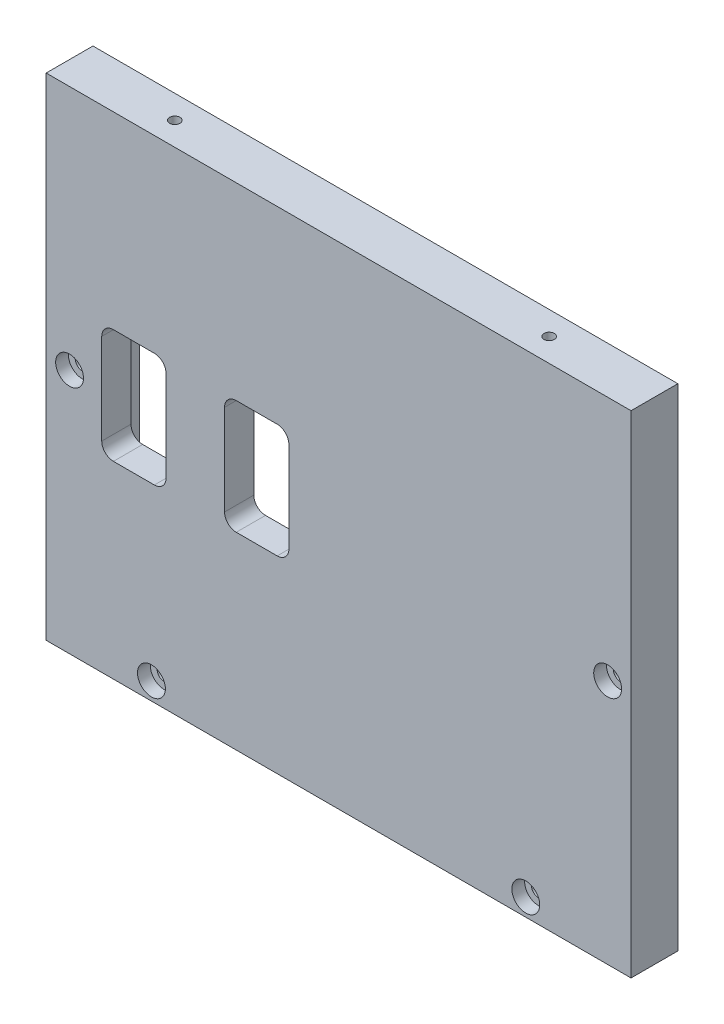
SolidWorks part; units mm, degrees
ref_plane "Front Plane" through (0, 0, 0) normal (0, 0, 1) x (1, 0, 0)
ref_plane "Top Plane" through (0, 0, 0) normal (0, 1, 0) x (1, 0, 0)
ref_plane "Right Plane" through (0, 0, 0) normal (1, 0, 0) x (0, 0, -1)
sketch "Sketch1" plane through (0, 0, 0) normal (0, 0, 1) x (1, 0, 0)
  line L1 (-50, 42) -> (50, 42)
  line L2 (-50, 42) -> (-50, -42)
  line L3 (-50, -42) -> (50, -42)
  line L4 (50, 42) -> (50, -42)
  line L5 (-50, 42) -> (50, -42) construction
  line L6 (-50, -42) -> (50, 42) construction
  point P0 (0, 0)
extrude "Boss-Extrude1" add sketch "Sketch1" along normal blind 8
sketch "Sketch2" plane through (0, 0, 8) normal (0, 0, 1) x (1, 0, 0)
  line L0 (-50, -42) -> (-50, -36) construction
  line L1 (-50, -36) -> (50, -36) construction
  line L2 (50, -42) -> (50, 42) construction
  line L3 (50, -36) -> (50, -42) construction
  line L4 (-50, -39) -> (-32, -39) construction
  line L5 (50, -39) -> (32, -39) construction
  point P12 (0, 0)
  point P13 (0, 0)
hole_wizard "CBORE for #2 Socket Head Cap Screw1" positions "3DSketch1" profile "Sketch3" counterbore size "#2" standard "ANSI Inch"
sketch3d "3DSketch1"
  point P0 (-32, -39, 8)
  point P3 (32, -39, 8)
sketch "Sketch3" plane through (-32, -39, 8) normal (1, 0, 0) x (0, -1, 0)
  line L0 (0, 0) -> (0, 13.0026)
  line L1 (0, 13.0026) -> (1.2192, 12.27)
  line L2 (1.2192, 12.27) -> (1.2192, 2.1844)
  line L3 (1.2192, 2.1844) -> (2.3812, 2.1844)
  line L4 (2.3812, 2.1844) -> (2.3812, 0)
  line L5 (2.3812, 0) -> (0, 0)
  line L10 (0, 13.0026) -> (-1.2192, 12.27) construction
  line L11 (0, -6.35) -> (0, 107.95) construction
  dimension "Hole Dia." = 2.4384
  dimension "Hole Depth" = 12.27
  dimension "C'Bore Dia." = 4.7625
  dimension "C'Bore Depth" = 2.1844
  dimension "Drill Angle" = 118
sketch "Sketch4" plane through (0, 0, 8) normal (0, 0, 1) x (1, 0, 0)
  line L0 (-50, -42) -> (-42, -42) construction
  line L1 (-42, -42) -> (-42, 42) construction
  line L2 (50, 42) -> (-50, 42) construction
  line L3 (-42, 42) -> (-50, 42) construction
  line L4 (50, -42) -> (42, -42) construction
  line L5 (42, -42) -> (42, 42) construction
  line L6 (42, 42) -> (50, 42) construction
  line L7 (46, -42) -> (46, 0) construction
  line L8 (-46, -42) -> (-46, 0) construction
hole_wizard "CBORE for #2 Socket Head Cap Screw2" positions "3DSketch2" profile "Sketch5" counterbore size "#2" standard "ANSI Inch"
sketch3d "3DSketch2"
  point P0 (-46, 0, 8)
  point P3 (46, 0, 8)
sketch "Sketch5" plane through (-46, 0, 8) normal (1, 0, 0) x (0, -1, 0)
  line L0 (0, 0) -> (0, 13.0026)
  line L1 (0, 13.0026) -> (1.2192, 12.27)
  line L2 (1.2192, 12.27) -> (1.2192, 2.1844)
  line L3 (1.2192, 2.1844) -> (2.3812, 2.1844)
  line L4 (2.3812, 2.1844) -> (2.3812, 0)
  line L5 (2.3812, 0) -> (0, 0)
  line L10 (0, 13.0026) -> (-1.2192, 12.27) construction
  line L11 (0, -6.35) -> (0, 107.95) construction
  dimension "Hole Dia." = 2.4384
  dimension "Hole Depth" = 12.27
  dimension "C'Bore Dia." = 4.7625
  dimension "C'Bore Depth" = 2.1844
  dimension "Drill Angle" = 118
sketch "Sketch6" plane through (0, 42, 0) normal (0, 1, 0) x (1, 0, 0)
  line L0 (-50, -4) -> (-32, -4) construction
  line L1 (-50, -8) -> (-50, 0) construction
  line L2 (50, -4) -> (32, -4) construction
  line L3 (50, -8) -> (50, 0) construction
hole_wizard "#2-56 Tapped Hole1" positions "3DSketch3" profile "Sketch7" tap size "#2-56" standard "ANSI Inch"
sketch3d "3DSketch3"
  point P0 (-32, 42, 4)
  point P3 (32, 42, 4)
sketch "Sketch7" plane through (-32, 42, 4) normal (1, 0, 0) x (0, 0, 1)
  line L0 (0, 0) -> (0, 12.5342)
  line L1 (0, 12.5342) -> (0.889, 12)
  line L2 (0.889, 12) -> (0.889, 0)
  line L5 (0.889, 0) -> (0, 0)
  line L10 (0, 12.5342) -> (-0.889, 12) construction
  line L11 (0, -6.35) -> (0, 107.95) construction
  dimension "Tap Drill Dia." = 1.778
  dimension "Tap Drill Depth" = 12
  dimension "Drill Angle" = 118
cosmetic thread "Hole Thread1" parameters "D1"=10, "D2"=2.1844
cosmetic thread "Hole Thread2" parameters "D1"=10, "D2"=2.1844
sketch "Sketch8" plane through (0, 0, 0) normal (0, 0, -1) x (-1, 0, 0)
  line L0 (-50, -42) -> (-50, -30) construction
  line L1 (-50, -30) -> (50, -30) construction
  line L2 (50, 42) -> (50, -42) construction
  line L3 (50, -30) -> (50, -42) construction
sketch "Sketch9" plane through (0, 0, 0) normal (0, 0, -1) x (-1, 0, 0)
  line L0 (50, -42) -> (42, -42) construction
  line L1 (42, -42) -> (42, 42) construction
  line L2 (-50, 42) -> (50, 42) construction
  line L3 (-50, -42) -> (-42, -42) construction
  line L4 (-42, -42) -> (-42, 42) construction
  line L5 (-50, 42) -> (-32, 42) construction
sketch "Sketch10" plane through (0, 0, 0) normal (0, 0, -1) x (-1, 0, 0)
  line L0 (-42, -42) -> (-37, -42) construction
  line L1 (-37, -42) -> (-37, 42) construction
  line L2 (-50, 42) -> (50, 42) construction
  line L3 (-37, -42) -> (-27, -42) construction
  line L4 (-27, -42) -> (-27, 42) construction
  line L5 (-27, -42) -> (3, -42) construction
  line L6 (3, -42) -> (3, 42) construction
  line L7 (3, -42) -> (7, -42) construction
  line L8 (7, -42) -> (7, 42) construction
sketch "Sketch12" plane through (0, 0, 0) normal (0, 0, -1) x (-1, 0, 0)
  line L0 (7, -42) -> (7, -30) construction
  line L1 (-50, -30) -> (50, -30) construction
  line L2 (7, -30) -> (42, -30) construction
  line L3 (42, -42) -> (42, 42) construction
  line L4 (42, -30) -> (42, 30) construction
  line L5 (42, 30) -> (7, 30) construction
  line L6 (7, -42) -> (7, 42) construction
  line L7 (7, 30) -> (7, -30) construction
  line L9 (7, 30) -> (42, 30)
  line L10 (7, 30) -> (7, -30)
  line L11 (7, -30) -> (42, -30)
  line L12 (42, 30) -> (42, -30)
extrude "Cut-Extrude3" cut sketch "Sketch12" against normal blind 3
fillet "Fillet1" radius 2 1 edges at (-7, 30, 1.5)
fillet "Fillet2" radius 2 1 edges at (-42, 30, 1.5)
fillet "Fillet3" radius 2 1 edges at (-42, -30, 1.5)
fillet "Fillet4" radius 2 1 edges at (-7, -30, 1.5)
sketch "Sketch13" plane through (0, 0, 3) normal (0, 0, -1) x (-1, 0, 0)
  line L0 (40, -30) -> (9, -30) construction
  line L1 (9, -30) -> (24.5, 0) construction
  line L2 (24.5, 0) -> (40, -30) construction
  line L3 (24.5, 0) -> (42, 0) construction
  line L4 (42, -28) -> (42, 28) construction
sketch "Sketch14" plane through (0, 0, 3) normal (0, 0, -1) x (-1, 0, 0)
  line L0 (24.5, 0) -> (7, 0) construction
  line L1 (7, 28) -> (7, -28) construction
sketch "Sketch15" plane through (0, 0, 3) normal (0, 0, -1) x (-1, 0, 0)
  line L0 (24.5, 0) -> (29.5, 0) construction
  line L1 (24.5, 0) -> (19.5, 0) construction
  line L2 (29.5, 0) -> (40.5, 0) construction
  line L3 (40.5, 0) -> (40.5, 9.75) construction
sketch "Sketch16" plane through (0, 0, 3) normal (0, 0, -1) x (-1, 0, 0)
  line L0 (19.5, 0) -> (8.5, 0) construction
  line L1 (19.5, 0) -> (19.5, -9.75) construction
  line L2 (8.5, 0) -> (8.5, 9.75) construction
  line L3 (29.5, 0) -> (29.5, -9.75) construction
  line L4 (8.5, 9.75) -> (19.5, 9.75)
  line L5 (8.5, 9.75) -> (8.5, -9.75)
  line L6 (8.5, -9.75) -> (19.5, -9.75)
  line L7 (19.5, 9.75) -> (19.5, -9.75)
sketch "Sketch17" plane through (0, 0, 3) normal (0, 0, -1) x (-1, 0, 0)
  line L1 (29.5, -9.75) -> (40.5, -9.75)
  line L2 (29.5, -9.75) -> (29.5, 9.75)
  line L3 (29.5, 9.75) -> (40.5, 9.75)
  line L4 (40.5, -9.75) -> (40.5, 9.75)
extrude "Cut-Extrude4" cut sketch "Sketch17" against normal blind 8 contours L2 L1 L4 L3
extrude "Cut-Extrude5" cut sketch "Sketch16" against normal blind 8
fillet "Fillet5" radius 2 2 edges at (-40.5, 9.75, 5.5) (-19.5, 9.75, 5.5)
fillet "Fillet6" radius 2 2 edges at (-29.5, 9.75, 5.5) (-8.5, 9.75, 5.5)
fillet "Fillet7" radius 2 2 edges at (-29.5, -9.75, 5.5) (-8.5, -9.75, 5.5)
fillet "Fillet8" radius 2 2 edges at (-40.5, -9.75, 5.5) (-19.5, -9.75, 5.5)
sketch "Sketch19" plane through (0, 0, 8) normal (0, 0, 1) x (1, 0, 0)
  line L0 (-38.5, 9.75) -> (-31.5, 9.75) construction
  line L1 (-38.5, 9.75) -> (-31.5, 9.75) construction
  line L2 (-31.5, 9.75) -> (-31.5, 12.5) construction
  line L3 (-31.5, 12.5) -> (-38.5, 12.5) construction
  line L4 (-38.5, 12.5) -> (-38.5, 9.75) construction
  line L5 (-38.5, 12.5) -> (-35, 12.5) construction
  line L6 (-35, 12.5) -> (-35, 9.75) construction
  line L7 (-17.5, 9.75) -> (-10.5, 9.75) construction
  line L8 (-10.5, 9.75) -> (-10.5, 12.5) construction
  line L9 (-10.5, 12.5) -> (-14, 12.5) construction
  line L10 (-14, 12.5) -> (-14, 9.75) construction
  line L11 (-10.5, -9.75) -> (-17.5, -9.75) construction
  line L12 (-17.5, -9.75) -> (-17.5, -12.5) construction
  line L13 (-17.5, -12.5) -> (-10.5, -12.5) construction
  line L14 (-10.5, -12.5) -> (-10.5, -9.75) construction
  line L15 (-10.5, -9.75) -> (-14, -9.75) construction
  line L16 (-14, -9.75) -> (-14, -12.5) construction
  line L17 (-38.5, -9.75) -> (-31.5, -9.75) construction
  line L18 (-31.5, -9.75) -> (-31.5, -12.5) construction
  line L19 (-31.5, -12.5) -> (-35, -12.5) construction
  line L20 (-35, -12.5) -> (-35, -9.75) construction
  arc A0 (-29.5, 7.75) -> (-31.5, 9.75) centre (-31.5, 7.75) ccw construction
